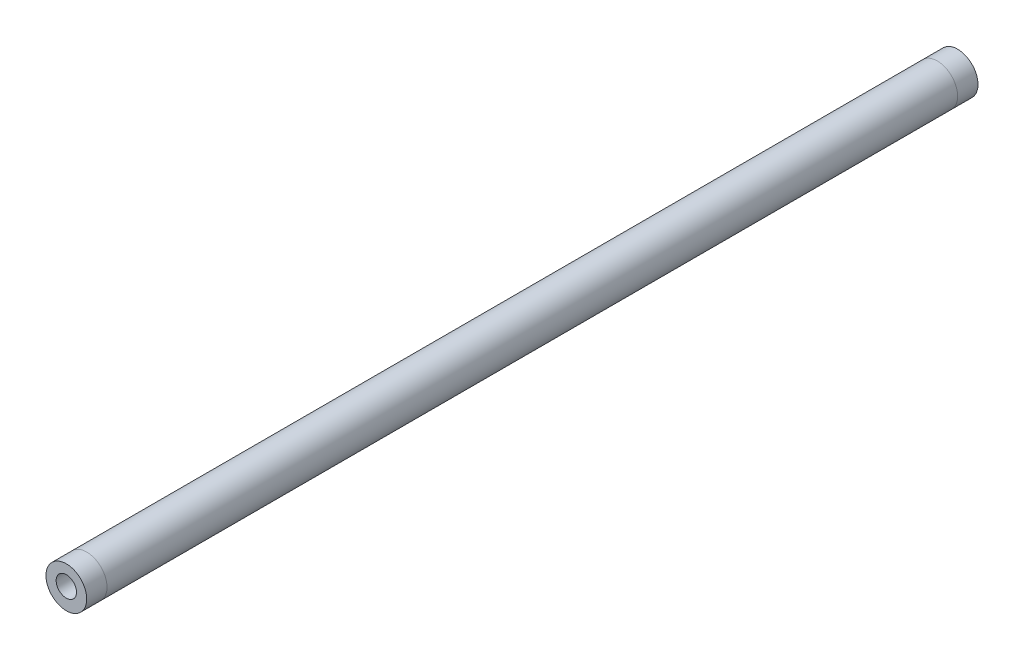
SolidWorks part; units mm, degrees
ref_plane "Front Plane" through (0, 0, 0) normal (0, 0, 1) x (1, 0, 0)
ref_plane "Top Plane" through (0, 0, 0) normal (0, 1, 0) x (1, 0, 0)
ref_plane "Right Plane" through (0, 0, 0) normal (1, 0, 0) x (0, 0, -1)
sketch "Axis" plane through (0, 0, 0) normal (0, 1, 0) x (1, 0, 0)
  line L0 (0, 0) -> (0, 21.8948) construction
  line L1 (0, 21.8948) -> (0, 299.8639) construction
  line L2 (0, 299.8639) -> (0, 321.7587) construction
  dimension "D1" = 21.8948
  dimension "D2" = 321.7587
sketch "Sketch2" plane through (0, 0, 0) normal (0, 0, 1) x (1, 0, 0)
  circle A0 centre (0, 0) radius 6.35
  circle A1 centre (0, 0.235) radius 3.175
  circle A2 centre (0, 0) radius 4.7625
  dimension "D1" = 12.7
  dimension "D2" = 6.35
  dimension "D3" = 9.525
extrude "Threaded Insert 1-1" add sketch "Sketch2" against normal blind 6.35 from vertex contours A0 A2 | A2 A1 region at (-6.1704, 0, 0) region at (-4.6278, 0, 0) starting at point (0, 0, -21.8948)
extrude "Threaded Insert 1-2" add sketch "Sketch2<5>" against normal blind 9.525 from surface contours A2 A1 region at (-4.6278, 0, 0) starting at face at (6.35, 0, -28.2448)
sketch "Sketch2<5>" plane through (0, 0, 0) normal (0, 0, 1) x (1, 0, 0) same geometry as "Sketch2"
extrude "Boss-Extrude4" add sketch "Sketch2<7>" along normal blind 6.35 from vertex separate body contours A0 A2 | A2 A1 region at (-6.1704, 0, 0) region at (-4.6278, 0, 0) starting at point (0, 0, -299.8639)
sketch "Sketch2<7>" plane through (0, 0, 0) normal (0, 0, 1) x (1, 0, 0) same geometry as "Sketch2"
extrude "Boss-Extrude5" add sketch "Sketch2<8>" along normal blind 9.525 from surface contours A2 A1 region at (-4.6278, 0, 0) starting at face at (6.35, 0, -293.5139)
sketch "Sketch2<8>" plane through (0, 0, 0) normal (0, 0, 1) x (1, 0, 0) same geometry as "Sketch2"
extrude "Boss-Extrude6" add sketch "Sketch2<9>" against normal up to surface (293.5139 mm away) from surface separate body contours A0 A2 region at (-6.1704, 0, 0) up to face at (6.35, 0, -293.5139) starting at face at (4.7625, 0, -28.2448)
sketch "Sketch2<9>" plane through (0, 0, 0) normal (0, 0, 1) x (1, 0, 0) same geometry as "Sketch2"
equation "\"Tube Outer Diameter\"= .5"
equation "\"Tube Inner Diameter\"= .375"
equation "\"Rod end Diameter\"= .25"
equation "\"Threaded Insert Out\"= .25"
equation "\"Threaded Insert In\"= .375'`"
equation "\"D1@Sketch2\"=\"Tube Outer Diameter\""
equation "\"D2@Sketch2\"=\"Rod end Diameter\""
equation "\"D1@Threaded Insert 1-1\" = \"Threaded Insert Out\""
equation "\"D3@Sketch2\"=\"Tube Inner Diameter\""
equation "\"D1@Threaded Insert 1-2\" = \"Threaded Insert In\""
equation "\"D1@Boss-Extrude4\"=\"Threaded Insert Out\""
equation "\"D1@Boss-Extrude5\"=\"Threaded Insert In\""
